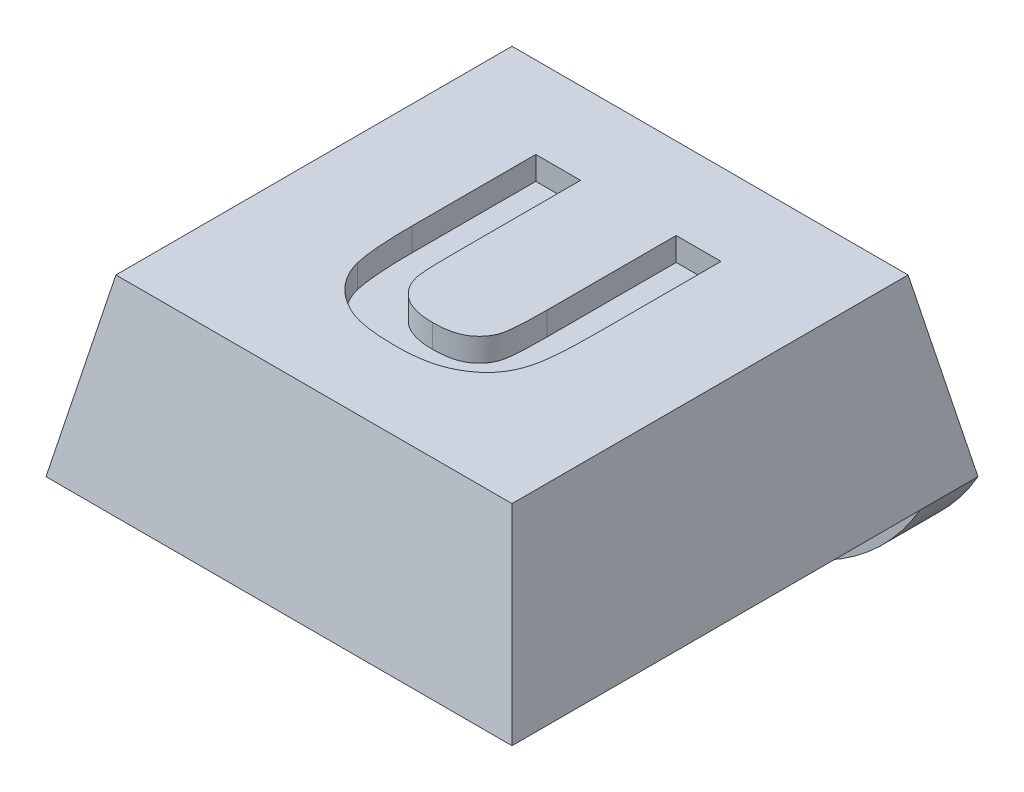
SolidWorks part; units mm, degrees
ref_plane "Front Plane" through (0, 0, 0) normal (0, 0, 1) x (1, 0, 0)
ref_plane "Top Plane" through (0, 0, 0) normal (0, 1, 0) x (1, 0, 0)
ref_plane "Right Plane" through (0, 0, 0) normal (1, 0, 0) x (0, 0, -1)
sketch "Sketch1" plane through (0, 0, 0) normal (0, 1, 0) x (1, 0, 0)
  line L1 (0, 0) -> (8, 0)
  line L2 (0, 0) -> (0, 8)
  line L3 (0, 8) -> (8, 8)
  line L4 (8, 0) -> (8, 8)
  dimension "D1" = 8
  dimension "D2" = 8
extrude "Boss-Extrude1" add sketch "Sketch1" along normal blind 3
sketch "Sketch2" plane through (0, 0, 0) normal (0, 0, 1) x (1, 0, 0)
  line L0 (0, 0) -> (0.6, 3)
  line L1 (0, 3) -> (8, 3) construction
  line L2 (0.6, 3) -> (0, 3)
  line L3 (0, 3) -> (0, 0)
  line L4 (8, 0) -> (7.4, 3)
  line L5 (7.4, 3) -> (8, 3)
  line L6 (8, 3) -> (8, 0)
  dimension "D1" = 0.6
  dimension "D2" = 0.6
extrude "Cut-Extrude1" cut sketch "Sketch2" against normal through all both and the other way through all
sketch "Sketch3" plane through (0, 0, 0) normal (1, 0, 0) x (0, 0, -1)
  line L0 (0, 0) -> (0.6, 3)
  line L1 (8, 3) -> (0, 3) construction
  line L2 (0.6, 3) -> (0, 3)
  line L3 (0, 3) -> (0, 0)
  line L4 (8, 3) -> (7.4, 3)
  line L5 (7.4, 3) -> (8, 0)
  line L6 (8, 3) -> (8, 0)
  dimension "D1" = 0.6
  dimension "D2" = 0.6
extrude "Cut-Extrude2" cut sketch "Sketch3" along normal blind 11
sketch "Sketch4" plane through (0, 0, 0) normal (0, -1, 0) x (1, 0, 0)
  line L0 (8, 0) -> (8, -8) construction
  line L3 (0, 0) -> (8, 0) construction
  circle A0 centre (4, -3.75) radius 1.8
  dimension "D1" = 3.6
  dimension "D2" = 4
  dimension "D3" = 3.75
extrude "Cut-Extrude3" cut sketch "Sketch4" against normal blind 0.8
sketch "Sketch5" plane through (0, 0, 0) normal (0, -1, 0) x (1, 0, 0)
  line L0 (8, 0) -> (8, -8) construction
  line L1 (0, -8) -> (8, -8)
  line L2 (0, -8) -> (0, -7)
  line L3 (0, -7) -> (8, -7)
  line L4 (8, -8) -> (8, -7)
  dimension "D1" = 1
extrude "Boss-Extrude2" add sketch "Sketch5" along normal blind 2
fillet "Fillet1" radius 4 2 edges at (8, -2, -7.5) (0, -2, -7.5)
sketch "Sketch6" plane through (0, 3, 0) normal (0, 1, 0) x (1, 0, 0)
  text T0 "U" font "Arial" height 4
extrude "Cut-Extrude4" cut sketch "Sketch6" against normal blind 0.4
